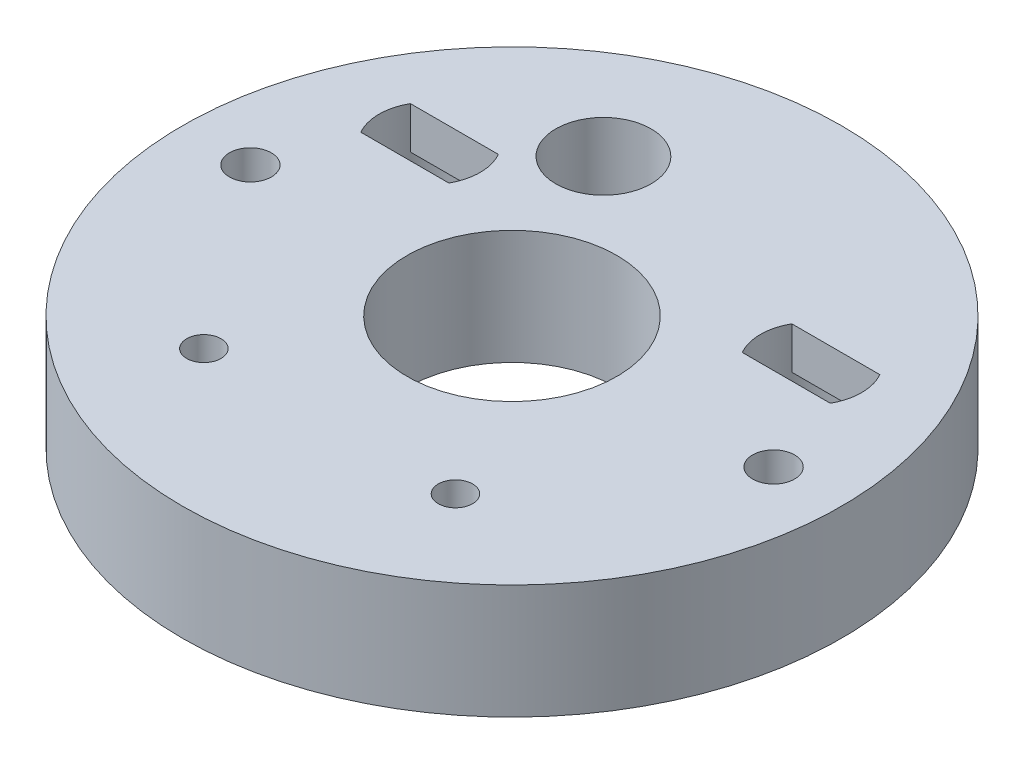
SolidWorks part; units mm, degrees
ref_plane "前视基准面" through (0, 0, 0) normal (0, 0, 1) x (1, 0, 0)
ref_plane "上视基准面" through (0, 0, 0) normal (0, 1, 0) x (1, 0, 0)
ref_plane "右视基准面" through (0, 0, 0) normal (1, 0, 0) x (0, 0, -1)
sketch "草图1" plane through (0, 0, 0) normal (0, 1, 0) x (1, 0, 0)
  line L0 (10, 5.6789) -> (-10, 5.6789) construction
  line L1 (0, 0) -> (0, 21.4139) construction
  line L2 (-6.595, -9.5611) -> (6.595, -9.5611) construction
  line L3 (-0.6445, -0.366) -> (22.2352, 12.6272) construction
  line L4 (0, 0) -> (2.6547, 0) construction
  circle A0 centre (0, 0) radius 17.28
  circle A1 centre (0, 0) radius 5 construction
  circle A2 centre (0, 0) radius 5.5
  circle A3 centre (10, 5.6789) radius 2.5 construction
  circle A4 centre (-10, 5.6789) radius 2.5 construction
  circle A5 centre (6.595, -9.5611) radius 1.76 construction
  circle A6 centre (-6.595, -9.5611) radius 1.76 construction
  circle A7 centre (-10, 5.6789) radius 2.65
  circle A8 centre (-6.595, -9.5611) radius 1.9
  circle A9 centre (6.595, -9.5611) radius 1.9
  circle A10 centre (10, 5.6789) radius 2.65
  point P14 (0, 5.6789)
  point P21 (0, -9.5611)
  dimension "D1" = 34.56
  dimension "D2" = 10
  dimension "D3" = 11
  dimension "D5" = 11.5
  dimension "D7" = 5
  dimension "D8" = 13.19
  dimension "D4" = 20
  dimension "D6" = 3.52
  dimension "D10" = 5.3
  dimension "D11" = 3.8
  dimension "D12" = 10
  dimension "D9" = 15.24
  dimension "D13" = 5.6789
extrude "凸台-拉伸1" add sketch "草图1" along normal blind 3.8
sketch "草图2" plane through (0, 3.8, 0) normal (0, 1, 0) x (1, 0, 0)
  line L0 (-7.35, 18.1851) -> (-7.35, -3.106) construction
  line L1 (0, -200000) -> (0, 200021.4139) construction
  line L2 (0, 0) -> (-3.9187, 0) construction
  circle A1 centre (0, 0) radius 17.28
  circle A2 centre (0, 0) radius 17.28 construction
  circle A3 centre (-10, 5.6789) radius 2.5 construction
  circle A4 centre (-4.85, 9.6447) radius 2.5
  circle A6 centre (-10, 5.6789) radius 2.65 construction
  dimension "D2" = 6.5
  dimension "D3" = 5
  dimension "D4" = 4.85
  dimension "D5" = 9.6447
  dimension "D1" = 0
extrude "切除-拉伸1" cut sketch "草图2" against normal through all
sketch "草图3" plane through (0, 3.8, 0) normal (0, 1, 0) x (1, 0, 0)
  line L0 (-12.3092, 4.3789) -> (-7.6908, 4.3789)
  line L1 (-12.3092, 6.9789) -> (-7.6908, 6.9789)
  line L2 (-10, 6.9789) -> (-10, 4.3789) construction
  line L3 (0, 0) -> (0, 3.4524) construction
  line L4 (12.3092, 4.3789) -> (7.6908, 4.3789)
  line L5 (12.3092, 6.9789) -> (7.6908, 6.9789)
  circle A0 centre (6.595, -9.5611) radius 1.9 construction
  circle A1 centre (0, 0) radius 17.28
  circle A2 centre (0, 0) radius 17.28
  circle A3 centre (-6.595, -9.5611) radius 1.9 construction
  circle A5 centre (-10, 5.6789) radius 2.65 construction
  circle A6 centre (0, 0) radius 5.5 construction
  circle A7 centre (-4.85, 9.6447) radius 2.5 construction
  circle A8 centre (6.595, -9.5611) radius 1.9 construction
  circle A9 centre (-6.595, -9.5611) radius 1.9 construction
  arc A11 (-12.3092, 6.9789) -> (-12.3092, 4.3789) centre (-10, 5.6789) ccw
  circle A12 centre (0, 0) radius 5.5
  circle A13 centre (-4.85, 9.6447) radius 2.5
  arc A14 (-7.6908, 4.3789) -> (-7.6908, 6.9789) centre (-10, 5.6789) ccw
  arc A15 (7.6908, 4.3789) -> (7.6908, 6.9789) centre (10, 5.6789) cw
  arc A16 (12.3092, 6.9789) -> (12.3092, 4.3789) centre (10, 5.6789) cw
  circle A17 centre (-6.595, -9.5611) radius 0.9
  circle A18 centre (6.595, -9.5611) radius 0.9
  dimension "D3" = 1.8
  dimension "D2" = 2.6
  dimension "D1" = 0
extrude "凸台-拉伸2" add sketch "草图3" along normal blind 2.2
sketch "草图4" plane through (0, 6, 0) normal (0, 1, 0) x (1, 0, 0)
  line L0 (0, 0) -> (-31.0846, 0) construction
  circle A0 centre (-13.717, 0) radius 1.1
  circle A1 centre (13.717, 0) radius 1.1
  dimension "D1" = 13.717
  dimension "D3" = 2.2
  dimension "D4" = 2.2
  dimension "D2" = 13.717
extrude "切除-拉伸2" cut sketch "草图4" against normal through all
sketch "草图5" plane through (0, 0, 0) normal (0, -1, 0) x (1, 0, 0)
  line L0 (0, 0) -> (27.0843, 0) construction
  circle A0 centre (13.717, 0) radius 1.6
  circle A1 centre (-13.717, 0) radius 1.6
  dimension "D1" = 3.2
  dimension "D2" = 3.2
extrude "切除-拉伸3" cut sketch "草图5" against normal blind 3
